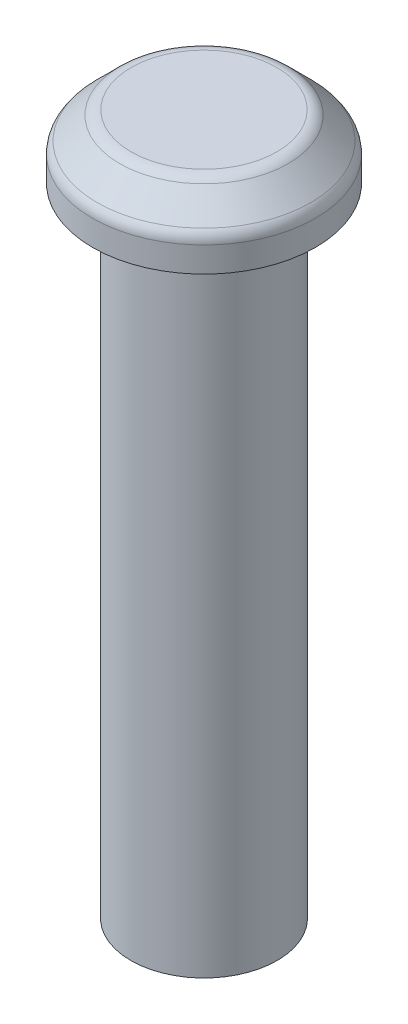
SolidWorks part; units mm, degrees
ref_plane "Front Plane" through (0, 0, 0) normal (0, 0, 1) x (1, 0, 0)
ref_plane "Top Plane" through (0, 0, 0) normal (0, 1, 0) x (1, 0, 0)
ref_plane "Right Plane" through (0, 0, 0) normal (1, 0, 0) x (0, 0, -1)
sketch "Sketch1" plane through (0, 0, 0) normal (0, 1, 0) x (1, 0, 0)
  circle A0 centre (0, 0) radius 2.3
  dimension "D1" = 4.6
extrude "Boss-Extrude1" add sketch "Sketch1" along normal blind 20
sketch "Sketch2" plane through (0, 20, 0) normal (0, 1, 0) x (1, 0, 0)
  circle A0 centre (0, 0) radius 3.5
  dimension "D1" = 7
extrude "Boss-Extrude2" add sketch "Sketch2" along normal blind 2
chamfer "Chamfer1" distance 1 angle 45 1 edges at (0, 22, 3.5)
fillet "Fillet1" radius 0.5 2 edges at (0, 21, 3.5) (0, 22, 2.5)
